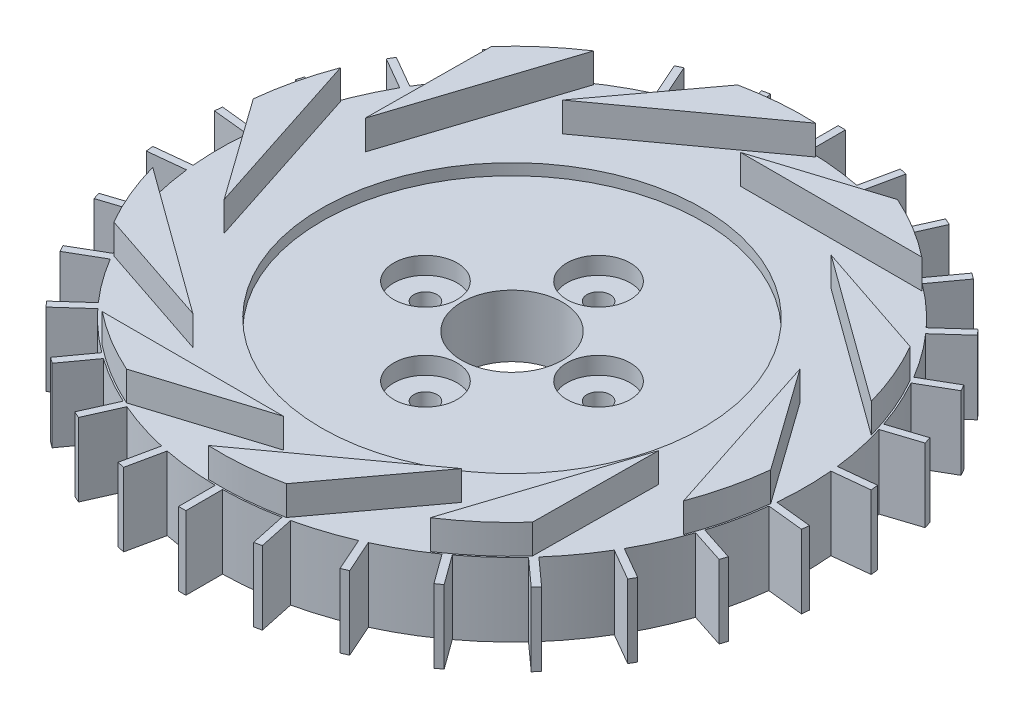
SolidWorks part; units mm, degrees
material "6061-T6 (SS)"
ref_plane "Front Plane" through (0, 0, 0) normal (0, 0, 1) x (1, 0, 0)
ref_plane "Top Plane" through (0, 0, 0) normal (0, 1, 0) x (1, 0, 0)
ref_plane "Right Plane" through (0, 0, 0) normal (1, 0, 0) x (0, 0, -1)
sketch "Sketch1" plane through (0, 0, 0) normal (1, 0, 0) x (0, 0, -1)
  line L0 (0, 26.2631) -> (0, -3.5886) construction
  line L1 (0, -3.5886) -> (-50.8, -3.5886)
  line L2 (-50.8, -3.5886) -> (-50.8, 9.1114)
  line L3 (-33.0001, 9.1114) -> (-50.8, 9.1114)
  line L4 (-33.0001, 9.1114) -> (-33.0001, 7.1515)
  line L5 (-33.0001, 7.1515) -> (0, 7.1515)
  line L6 (0, 7.1515) -> (0, -3.5886)
  dimension "D1" = 33.0001
  dimension "D2" = 50.8
  dimension "D3" = 1.96
  dimension "D4" = 12.7
revolve "Revolve1" add sketch "Sketch1" angle 360 about L0
sketch "Sketch2" plane through (0, 9.1114, 0) normal (0, 1, 0) x (1, 0, 0)
  line L8 (0, 39.6001) -> (19.9397, 39.6001) construction
  line L9 (0, 39.6001) -> (20.682, 46.1211)
  line L10 (0, 39.6001) -> (31.4123, 39.6001)
  arc A3 (20.682, 46.1211) -> (31.4123, 39.6001) centre (0, 0) cw
  circle A5 centre (0, 0) radius 33.0001 construction
  circle A7 centre (0, 0) radius 39.6001 construction
  point P6 (0, 0)
  point P9 (-2.4416, -40.4611)
  point P10 (0, 0)
  point P11 (0, 0)
  point P12 (0, 0)
  dimension "D1" = 66.0001
  dimension "D2" = 79.2001
  dimension "D4" = 50.546
  dimension "D3" = 17.5
extrude "Boss-Extrude1" add sketch "Sketch2" along normal blind 5.08
pattern_circular "CirPattern1" count 10 over 360 about axis through (0, 9.1114, 0) along (0, 1, 0) of "Boss-Extrude1"
ref_plane "Plane1" through (0, 0, 49.53) normal (0, 0, 1) x (1, 0, 0)
sketch "Sketch3" plane through (0, 0, 49.53) normal (0, 0, 1) x (1, 0, 0)
  line L0 (0, 0) -> (0, 9.7621) construction
  line L1 (0, -9.779) -> (0, 9.779) construction
  line L6 (-50.8, -3.5886) -> (50.8, -3.5886) construction
  line L13 (10.3772, 9.1114) -> (23.2763, 9.1114) construction
  line L14 (-0.635, -3.5886) -> (0.635, -3.5886)
  line L15 (-0.635, -3.5886) -> (-0.635, 9.1114)
  line L16 (-0.635, 9.1114) -> (0.635, 9.1114)
  line L17 (0.635, -3.5886) -> (0.635, 9.1114)
  point P11 (0, 9.1114)
  dimension "D1" = 1.27
extrude "Boss-Extrude2" add sketch "Sketch3" along normal blind 7.62 and the other way blind 0.254
pattern_circular "CirPattern16" count 30 over 360 about axis through (0, -3.5886, 0) along (0, 1, 0) of "Boss-Extrude2"
sketch "Sketch4" plane through (0, 7.1515, 0) normal (0, 1, 0) x (1, 0, 0)
  circle A0 centre (0, 0) radius 8.7312
  dimension "D1" = 17.4625
extrude "Cut-Extrude1" cut sketch "Sketch4" against normal up to next
sketch "Sketch5" plane through (0, -3.5886, 0) normal (0, -1, 0) x (-1, 0, 0)
  circle A0 centre (0, 0) radius 44.45
  dimension "D1" = 88.9
extrude "Cut-Extrude2" cut sketch "Sketch5" against normal blind 6.35
sketch "Sketch6" plane through (0, 2.7614, 0) normal (0, -1, 0) x (1, 0, 0)
  circle A0 centre (0, 0) radius 19.05
  circle A1 centre (0, 0) radius 8.7312 construction
  circle A2 centre (0, 0) radius 8.7312
  dimension "D1" = 38.1
extrude "Boss-Extrude3" add sketch "Sketch6" along normal up to surface (6.35 mm away) up to face at (0, -3.5886, -44.45)
sketch "Sketch9" plane through (0, 7.1515, 0) normal (0, 1, 0) x (1, 0, 0)
  circle A0 centre (0, 15) radius 2
  dimension "D1" = 4
  dimension "D2" = 15
extrude "Cut-Extrude3" cut sketch "Sketch9" against normal up to next
pattern_circular "CirPattern17" count 4 over 360 about axis through (0, 7.1515, 0) along (0, 1, 0) of "Cut-Extrude3"
ref_plane "Plane2" through (51.9838, 0, -23.1447) normal (-0.9135, 0, 0.4067) x (0.4067, 0, 0.9135)
sketch "Sketch10" plane through (51.9838, 0, -23.1447) normal (-0.9135, 0, 0.4067) x (0.4067, 0, 0.9135)
  line L0 (3.175, -3.5886) -> (3.175, -0.4136)
  line L1 (-46.1462, -3.5886) -> (-41.4681, -3.5886) construction
  line L2 (-3.175, -0.4136) -> (-3.175, -3.5886)
  line L3 (-3.175, -3.5886) -> (3.175, -3.5886)
  arc A0 (3.175, -0.4136) -> (-3.175, -0.4136) centre (0, -0.4136) ccw
  dimension "D1" = 3.175
  dimension "D2" = 3.175
sketch "Sketch11" plane through (0, 7.1515, 0) normal (0, 1, 0) x (1, 0, 0)
  circle A0 centre (0, -15) radius 5.5
  circle A1 centre (-15, 0) radius 5.5
  circle A2 centre (0, 15) radius 5.5
  circle A3 centre (15, 0) radius 5.5
  dimension "D1" = 11
extrude "Cut-Extrude5" cut sketch "Sketch11" against normal blind 3
ref_plane "Plane3" through (0, 16.7314, 0) normal (0, 1, 0) x (1, 0, 0)
ref_axis "Axis4" through (0, -3.5886, 0) along (0, 1, 0)
ref_point "Point1"
